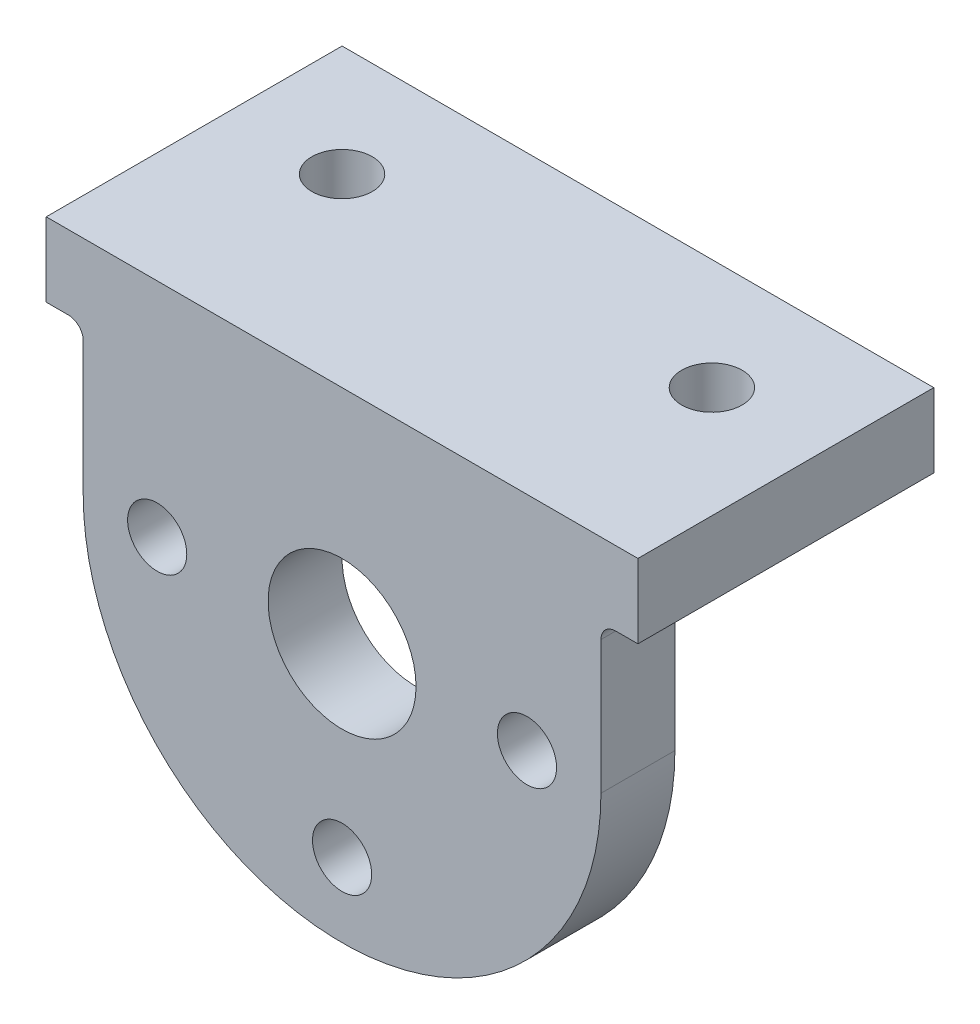
SolidWorks part; units mm, degrees
ref_plane "Front Plane" through (0, 0, 0) normal (0, 0, 1) x (1, 0, 0)
ref_plane "Top Plane" through (0, 0, 0) normal (0, 1, 0) x (1, 0, 0)
ref_plane "Right Plane" through (0, 0, 0) normal (1, 0, 0) x (0, 0, -1)
sketch "Sketch1" plane through (0, 0, 0) normal (0, 0, 1) x (1, 0, 0)
  line L0 (50.8, 0) -> (-50.8, 0)
  line L1 (-50.8, 0) -> (-50.8, -12.7)
  line L2 (-50.8, -12.7) -> (-44.45, -12.7)
  line L3 (-44.45, -12.7) -> (-44.45, -38.1)
  line L4 (0, -55) -> (0, 55) construction
  line L5 (44.45, -12.7) -> (44.45, -38.1)
  line L6 (50.8, -12.7) -> (44.45, -12.7)
  line L7 (50.8, 0) -> (50.8, -12.7)
  line L8 (-44.45, -12.7) -> (44.45, -12.7)
  arc A0 (-44.45, -38.1) -> (44.45, -38.1) centre (0, -38.1) ccw
  point P4 (0, 0)
  dimension "D1" = 101.6
  dimension "D2" = 12.7
  dimension "D3" = 25.4
  dimension "D4" = 6.35
extrude "Boss-Extrude1" add sketch "Sketch1" along normal blind 12.7 contours L3 A0 L5 L8 | L2 L8 L6 L7 L0 L1 region at (0, -6.35, 0) region at (0, -43.6715, 0)
extrude "Boss-Extrude2" add sketch "Sketch1<4>" against normal blind 38.1 contours L2 L8 L6 L7 L0 L1 region at (0, -6.35, 0)
sketch "Sketch1<4>" plane through (0, 0, 0) normal (0, 0, 1) x (1, 0, 0) same geometry as "Sketch1"
sketch "Sketch3" plane through (0, -12.7, 0) normal (0, -1, 0) x (1, 0, 0)
  line L0 (-50.8, 12.7) -> (-50.8, -38.1) construction
  line L1 (-50.8, -38.1) -> (50.8, -38.1) construction
  circle A0 centre (-31.75, -19.05) radius 5.1879
  circle A1 centre (31.75, -19.05) radius 5.1879
  point P8 (0, 0)
  dimension "D4" = 10.3759
  dimension "D1" = 19.05
  dimension "D2" = 19.05
  dimension "D3" = 82.55
sketch "Sketch4" plane through (0, 0, 12.7) normal (0, 0, 1) x (1, 0, 0)
  line L0 (-50.8, -12.7) -> (-44.45, -12.7) construction
  line L1 (-50.8, 0) -> (-50.8, -12.7) construction
  circle A0 centre (0, -38.1) radius 12.7
  circle A1 centre (-31.75, -38.1) radius 5.08
  circle A2 centre (31.75, -38.1) radius 5.08
  circle A3 centre (0, -69.85) radius 5.08
  point P8 (0, 0)
  point P9 (0, 0)
  point P12 (-10.4072, -38.1)
  point P13 (-4.5714, -38.1)
  point P15 (-27.5256, -38.1)
  dimension "D1" = 25.4
  dimension "D2" = 10.16
  dimension "D4" = 19.05
  dimension "D3" = 25.4
  dimension "D5" = 82.55
  dimension "D6" = 57.15
extrude "Cut-Extrude1" cut sketch "Sketch4" against normal through all
extrude "Cut-Extrude2" cut sketch "Sketch3" against normal through all
fillet "Fillet1" radius 2.54 3 edges at (0, -12.7, 0) (44.45, -12.7, 6.35) (-44.45, -12.7, 6.35)
